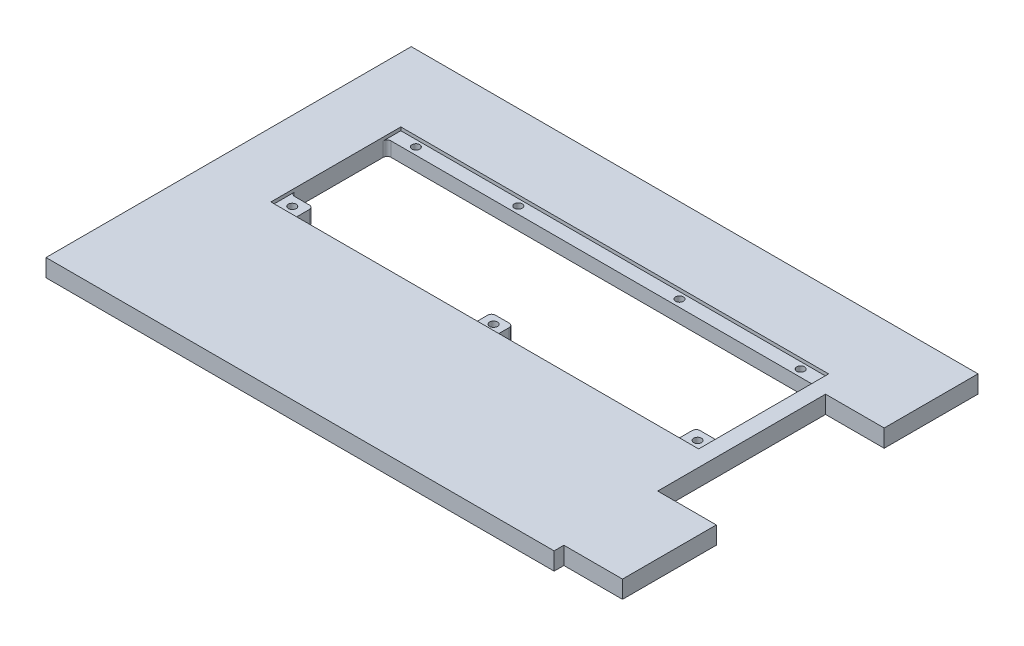
SolidWorks part; units mm, degrees
ref_plane "Front Plane" through (0, 0, 0) normal (0, 0, 1) x (1, 0, 0)
ref_plane "Top Plane" through (0, 0, 0) normal (0, 1, 0) x (1, 0, 0)
ref_plane "Right Plane" through (0, 0, 0) normal (1, 0, 0) x (0, 0, -1)
sketch "Sketch1" plane through (0, 0, 0) normal (0, 1, 0) x (1, 0, 0)
  line L1 (-15, 0) -> (245, 0)
  line L2 (-15, 0) -> (-15, 186.9)
  line L3 (-15, 186.9) -> (245, 186.9)
  line L4 (245, 0) -> (245, 186.9)
  dimension "D1" = 186.9
  dimension "D2" = 260
extrude "Boss-Extrude1" add sketch "Sketch1" along normal blind 9
sketch "Sketch2" plane through (0, 0, 0) normal (0, 1, 0) x (1, 0, 0)
  line L0 (245, 186.9) -> (-15, 186.9) construction
  line L1 (17.91, 148.65) -> (236.81, 148.65)
  line L2 (17.91, 148.65) -> (17.91, 82.15)
  line L3 (17.91, 82.15) -> (236.81, 82.15)
  line L4 (236.81, 148.65) -> (236.81, 82.15)
  line L5 (-15, 186.9) -> (-15, 0) construction
  dimension "D1" = 38.25
  dimension "D2" = 32.91
  dimension "D3" = 66.5
  dimension "D4" = 218.9
extrude "Cut-Extrude1" cut sketch "Sketch2" along normal blind 9
sketch "Sketch3" plane through (0, 9, 0) normal (0, 1, 0) x (1, 0, 0)
  line L0 (236.81, 148.65) -> (17.91, 148.65) construction
  line L1 (17.91, 148.65) -> (17.91, 82.15) construction
  line L2 (17.91, 82.15) -> (236.81, 82.15) construction
  circle A0 centre (28.91, 145.35) radius 2
  circle A1 centre (81.31, 145.35) radius 2
  circle A2 centre (163.81, 145.35) radius 2
  circle A3 centre (225.81, 145.35) radius 2
  circle A4 centre (23.66, 87.35) radius 2
  circle A5 centre (127.36, 86.65) radius 2
  circle A6 centre (231.06, 87.35) radius 2
  dimension "D3" = 4
  dimension "D4" = 3.3
  dimension "D6" = 3.3
  dimension "D8" = 3.3
  dimension "D10" = 5.2
  dimension "D12" = 4.5
  dimension "D14" = 5.2
  dimension "D1" = 3.3
  dimension "D2" = 11
  dimension "D5" = 52.4
  dimension "D7" = 82.5
  dimension "D9" = 62
  dimension "D11" = 5.75
  dimension "D13" = 103.7
  dimension "D15" = 103.7
sketch "Sketch4" plane through (0, 0, 0) normal (0, 1, 0) x (1, 0, 0)
  line L0 (236.81, 82.15) -> (236.81, 148.65) construction
  line L1 (17.91, 148.65) -> (236.81, 148.65)
  line L2 (17.91, 148.65) -> (17.91, 141.65)
  line L3 (17.91, 141.65) -> (236.81, 141.65)
  line L4 (236.81, 148.65) -> (236.81, 141.65)
  line L5 (17.91, 82.15) -> (236.81, 82.15) construction
  line L6 (236.81, 82.15) -> (225.31, 82.15)
  line L7 (236.81, 82.15) -> (236.81, 92.35)
  line L8 (236.81, 92.35) -> (225.31, 92.35)
  line L9 (225.31, 82.15) -> (225.31, 92.35)
  line L10 (121.86, 82.15) -> (132.86, 82.15)
  line L11 (121.86, 82.15) -> (121.86, 91.15)
  line L12 (121.86, 91.15) -> (132.86, 91.15)
  line L13 (132.86, 82.15) -> (132.86, 91.15)
  line L15 (17.91, 82.15) -> (29.41, 82.15)
  line L16 (17.91, 82.15) -> (17.91, 92.35)
  line L17 (17.91, 92.35) -> (29.41, 92.35)
  line L18 (29.41, 82.15) -> (29.41, 92.35)
  dimension "D1" = 7
  dimension "D2" = 5
  dimension "D3" = 5.75
  dimension "D4" = 4.5
  dimension "D5" = 5.5
  dimension "D6" = 5.5
  dimension "D7" = 5.75
  dimension "D8" = 5
extrude "Boss-Extrude2" add sketch "Sketch4" along normal blind 7.3
extrude "Cut-Extrude2" cut sketch "Sketch3" against normal blind 6.6
fillet "Fillet1" radius 2 12 edges at (17.91, 3.65, -92.35) (29.41, 3.65, -82.15) (29.41, 3.65, -92.35) (17.91, 3.65, -141.65) (236.81, 3.65, -141.65) (236.81, 3.65, -92.35) (225.31, 3.65, -82.15) (225.31, 3.65, -92.35) (121.86, 3.65, -82.15) (132.86, 3.65, -82.15) (132.86, 3.65, -91.15) (121.86, 3.65, -91.15)
sketch "Sketch5" plane through (245, 0, 0) normal (1, 0, 0) x (0, 0, -1)
  line L0 (0, 0) -> (186.9, 0) construction
  line L1 (5, 9) -> (53, 9)
  line L2 (5, 9) -> (5, 0)
  line L3 (5, 0) -> (53, 0)
  line L4 (53, 9) -> (53, 0)
  line L6 (186.9, 9) -> (138.9, 9)
  line L7 (186.9, 9) -> (186.9, 0)
  line L8 (186.9, 0) -> (138.9, 0)
  line L9 (138.9, 9) -> (138.9, 0)
  dimension "D1" = 48
  dimension "D2" = 48
extrude "Boss-Extrude3" add sketch "Sketch5" along normal blind 30
